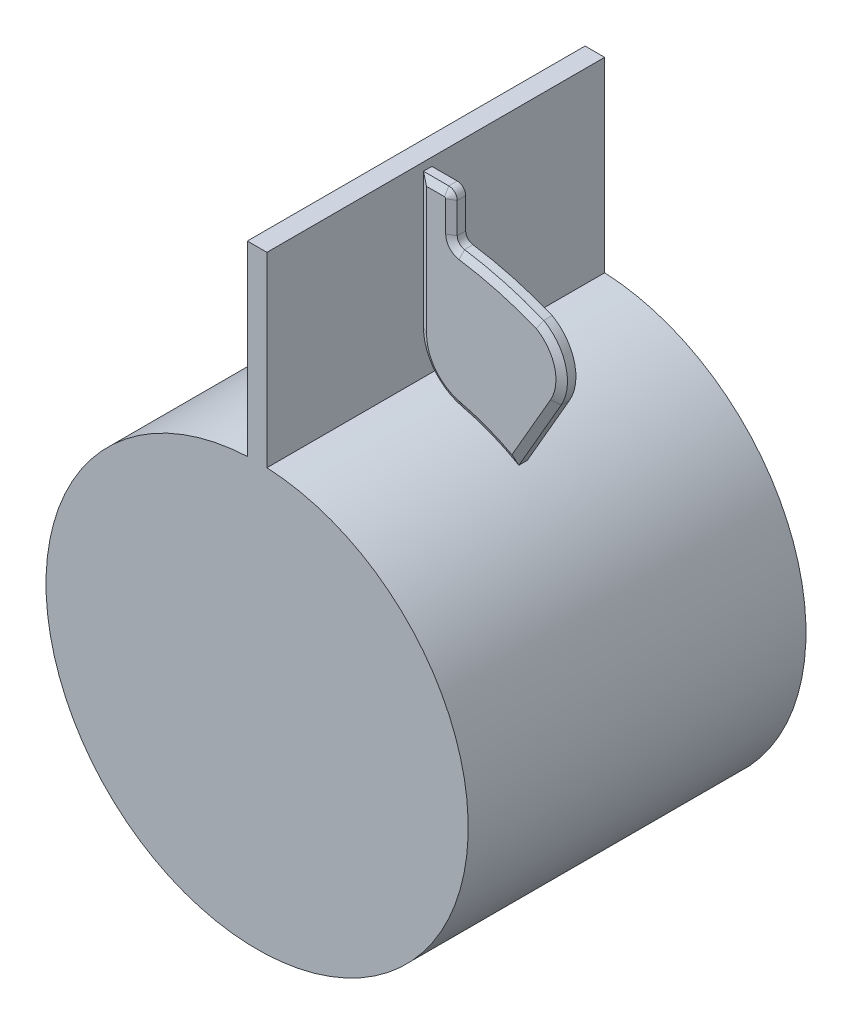
SolidWorks part; units mm, degrees
other "Markup1"
sketch "Sketch3" plane through (79.375, -79.375, 63.5) normal (0.9972, -0.0732, 0.0183) x (0.0054, -0.1724, -0.985)
ref_plane "Front Plane" through (0, 0, 0) normal (0, 0, 1) x (1, 0, 0)
ref_plane "Top Plane" through (0, 0, 0) normal (0, 1, 0) x (1, 0, 0)
ref_plane "Right Plane" through (0, 0, 0) normal (1, 0, 0) x (0, 0, -1)
sketch "Sketch1" plane through (0, 0, 0) normal (0, 0, 1) x (1, 0, 0)
  line L0 (0, 0) -> (0, 152.4) construction
  line L1 (16.51, 131.8891) -> (16.51, 143.3585)
  line L2 (0, 0) -> (152.4, 0) construction
  line L3 (3.81, 146.5335) -> (3.81, 95.7335)
  line L4 (3.81, 146.5335) -> (13.335, 146.5335)
  line L6 (3.81, 146.5335) -> (16.51, 146.5335) construction
  line L7 (16.51, 143.3585) -> (16.51, 146.5335) construction
  line L11 (3.81, 146.5335) -> (0, 146.5335) construction
  line L12 (39.6875, 68.7408) -> (55.5625, 96.2371)
  line L13 (40.1265, 105.1491) -> (55.5625, 96.2371) construction
  line L14 (40.1265, 105.1491) -> (49.0385, 120.5851) construction
  line L15 (0, 0) -> (107.7631, 186.6511) construction
  circle A0 centre (0, 0) radius 79.375 construction
  arc A1 (19.2163, 128.7488) -> (49.0385, 120.5851) centre (0, 0) cw
  arc A2 (19.2163, 128.7488) -> (16.51, 131.8891) centre (19.685, 131.8891) cw
  arc A7 (13.335, 146.5335) -> (16.51, 143.3585) centre (13.335, 143.3585) cw
  arc A8 (18.4355, 77.2044) -> (39.6875, 68.7408) centre (0, 0) cw
  arc A9 (3.81, 95.7335) -> (18.4355, 77.2044) centre (22.86, 95.7335) ccw
  arc A10 (55.5625, 96.2371) -> (49.0385, 120.5851) centre (40.1265, 105.1491) ccw
  dimension "D1" = 158.75
  dimension "D5" = 19.05
  dimension "D6" = 3.175
  dimension "D7" = 90
  dimension "D9" = 31.75
  dimension "D10" = 12.7
  dimension "D11" = 50.8
  dimension "D2" = 152.4
  dimension "D3" = 152.4
  dimension "D4" = 3.81
  dimension "D8" = 50.8
  dimension "D12" = 60
extrude "Boss-Extrude1" add sketch "Sketch1" along normal blind 6.35 contours A9 A8 A1 A2 L1 A7 L4 L3 region at (27.2183, 104.7652, 0)
sketch "Sketch2" plane through (0, 0, 0) normal (0, 0, 1) x (1, 0, 0)
  line L0 (0, 0) -> (0, 149.4418) construction
  line L1 (3.683, 149.4418) -> (-3.683, 149.4418)
  line L2 (-3.683, 149.4418) -> (-3.683, 79.2895)
  line L3 (3.683, 149.4418) -> (3.683, 79.2895)
  arc A1 (-3.683, 79.2895) -> (3.683, 79.2895) centre (0, 0) ccw
  point P7 (0, 149.4418)
  dimension "D2" = 79.375
  dimension "D1" = 7.366
extrude "Boss-Extrude2" add sketch "Sketch2" along normal mid plane 127 separate body
chamfer "Chamfer1" distance 2.7496 angle 30 10 edges at (29.368, 73.7422, 6.35) (7.9069, 83.9306, 6.35) (3.81, 121.1335, 6.35) (8.5725, 146.5335, 6.35) (15.5801, 145.6036, 6.35) (16.51, 137.6238, 6.35) (17.2799, 129.8163, 6.35) (34.3706, 125.5555, 6.35) (57.3431, 109.7622, 6.35) (47.625, 82.4889, 6.35) first distance on face at (23.8366, 115.619, 6.35)
chamfer "Chamfer2" distance 2.7496 angle 30 10 edges at (57.3431, 109.7622, 0) (34.3706, 125.5555, 0) (17.2799, 129.8163, 0) (16.51, 137.6238, 0) (15.5801, 145.6036, 0) (8.5725, 146.5335, 0) (3.81, 121.1335, 0) (7.9069, 83.9306, 0) (29.368, 73.7422, 0) (47.625, 82.4889, 0) first distance on face at (23.8366, 115.619, 0)
